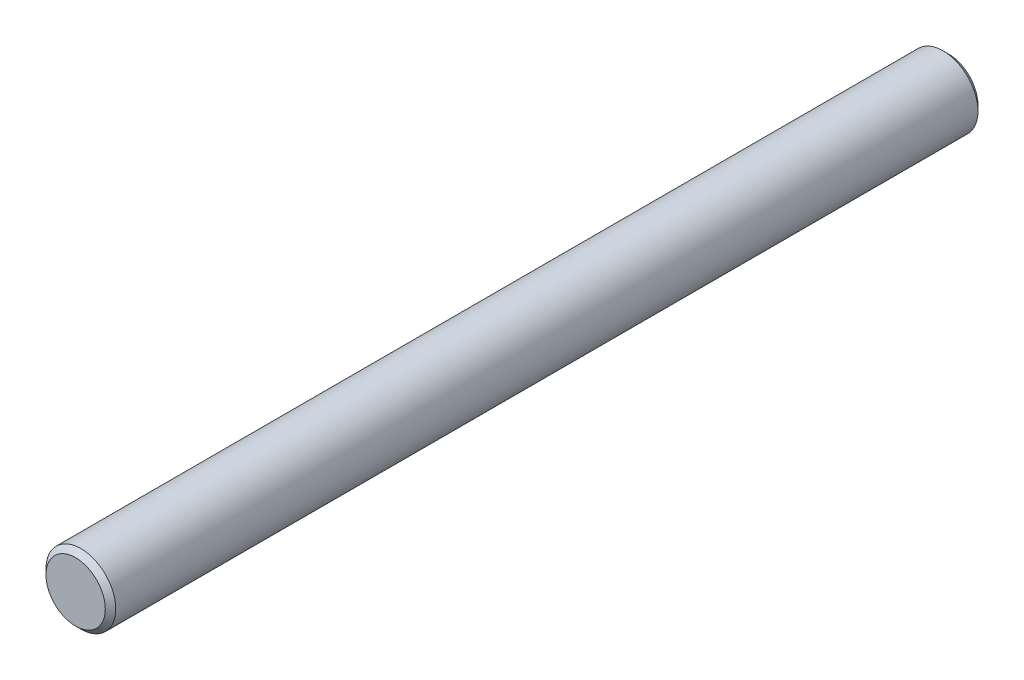
SolidWorks part; units mm, degrees
ref_plane "Front Plane" through (0, 0, 0) normal (0, 0, 1) x (1, 0, 0)
ref_plane "Top Plane" through (0, 0, 0) normal (0, 1, 0) x (1, 0, 0)
ref_plane "Right Plane" through (0, 0, 0) normal (1, 0, 0) x (0, 0, -1)
sketch "Sketch1" plane through (0, 0, 0) normal (0, 0, 1) x (1, 0, 0)
  line L0 (-4, 0) -> (4, 0) construction
  line L5 (0, 4) -> (0, -4) construction
  circle A1 centre (0, 0) radius 4
  point P7 (-4, 0)
  point P8 (4, 0)
  point P12 (0, -4)
  point P13 (0, 4)
  dimension "Diameter" = 8
sketch "Sketch2" plane through (0, 0, 0) normal (1, 0, 0) x (0, 0, -1)
  line L10 (-50, 0) -> (50, 0) construction
  line L11 (50, -4) -> (-50, -4)
  line L12 (50, -4) -> (50, 4)
  line L13 (50, 4) -> (-50, 4)
  line L14 (-50, -4) -> (-50, 4)
  line L15 (-40, 4) -> (-40, -4)
  line L16 (40, 4) -> (40, -4)
  line L17 (-40, 0) -> (40, 0) construction
  line L18 (-49.4, 4) -> (-50, 3.4) construction
  point P0 (0, 0)
  point P4 (0, 0)
  point P28 (0, 0)
  dimension "Chamfer Typ," = 45
  dimension "Length" = 100
  dimension "Chamfer Length" = 0.6
  dimension "D1" = 10
sketch "Sketch3" plane through (0, 0, 0) normal (0, 0, 1) x (1, 0, 0)
  circle A0 centre (0, 0) radius 4 construction
  circle A1 centre (0, 0) radius 4
extrude "Boss-Extrude1" add sketch "Sketch3" along normal up to vertex (-50 mm away) and the other way up to vertex (50 mm away) up to point (0, 4, -50) other way up to point (0, 4, -50)
chamfer "Chamfer1" distance 0.6 angle 45 2 edges at (4, 0, -50) (4, 0, 50)
ref_axis "Axis1" through (0, 0, 49.4) along (0, 0, -1)
equation "\"D1@Chamfer1\"=\"Chamfer Length@Sketch2\""
equation "\"D2@Chamfer1\"=\"Chamfer Typ,@Sketch2\""
equation "\"Chamfer Length@Sketch2\" = \"Diameter@Sketch1\" * .075"
